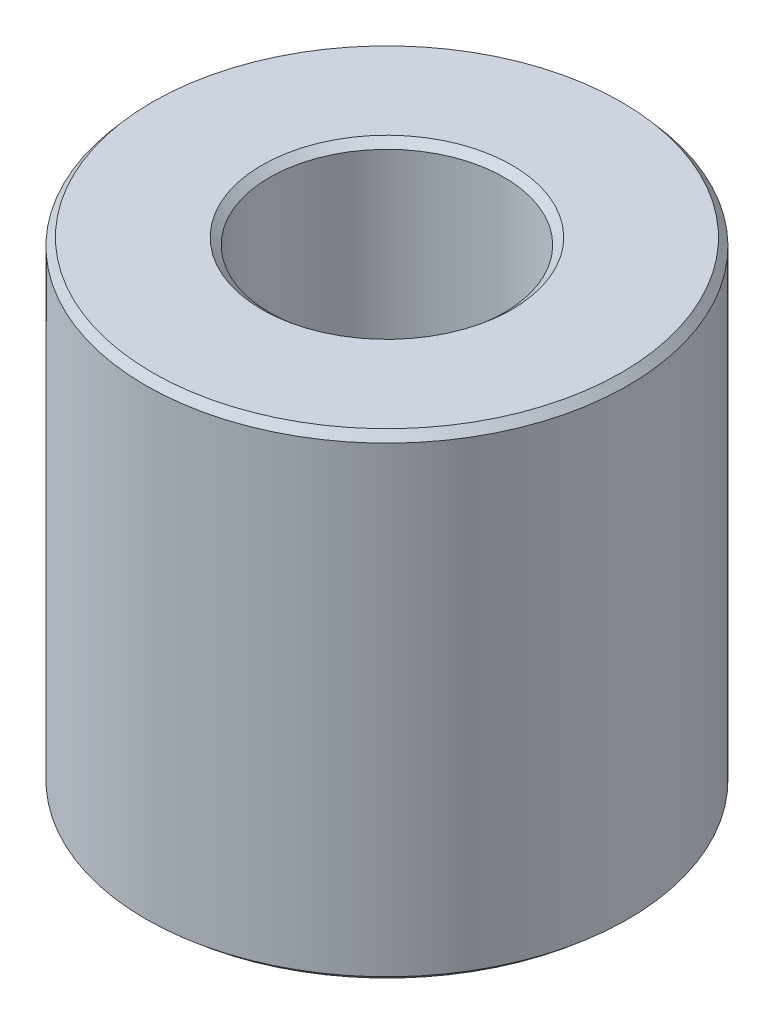
SolidWorks part; units mm, degrees
ref_plane "Front Plane" through (0, 0, 0) normal (0, 0, 1) x (1, 0, 0)
ref_plane "Top Plane" through (0, 0, 0) normal (0, 1, 0) x (1, 0, 0)
ref_plane "Right Plane" through (0, 0, 0) normal (1, 0, 0) x (0, 0, -1)
sketch "Sketch1" plane through (0, 0, 0) normal (0, 1, 0) x (1, 0, 0)
  circle A0 centre (0, 0) radius 10
  dimension "SLEEVE_OD" = 20
extrude "Boss-Extrude1" add sketch "Sketch1" along normal blind 19.7639
sketch "Sketch2" plane through (0, 0, 0) normal (0, 1, 0) x (1, 0, 0)
  circle A0 centre (0, 0) radius 4.8619
  dimension "BORE_D" = 9.7239
extrude "Cut-Extrude1" cut sketch "Sketch2" along normal through all
chamfer "Chamfer1" distance 0.3236 angle 40.61 4 edges at (0, 19.7639, 4.8619) (0, 0, 4.8619) (0, 0, 10) (0, 19.7639, 10) first distance on face at (0, 19.7639, 4.8619) first distance on face at (0, 0, 4.8619) first distance on face at (0, 19.7639, 10)
